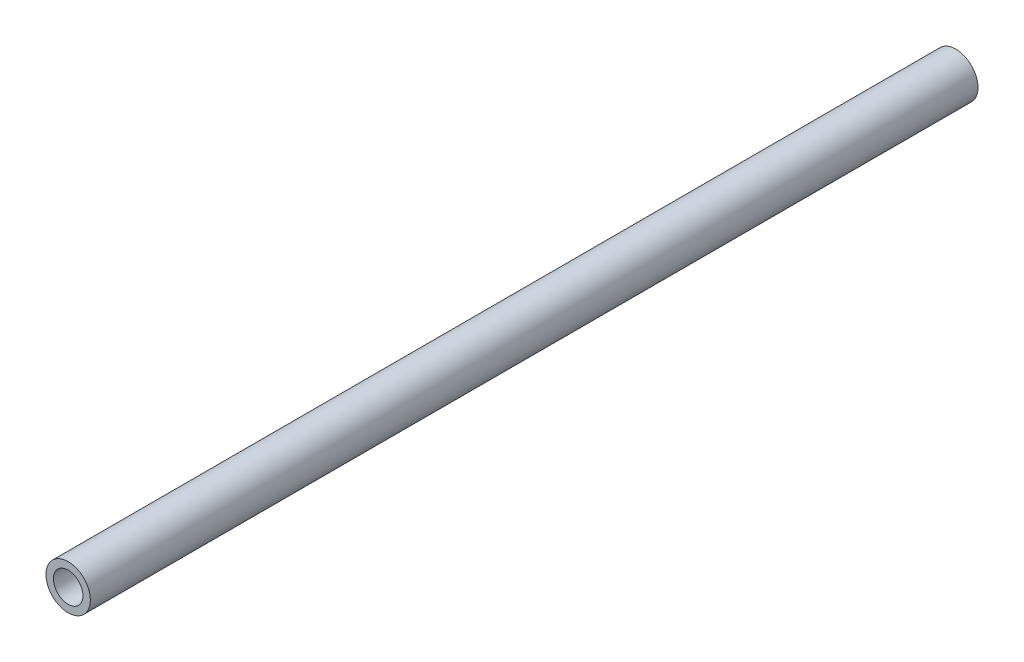
SolidWorks part; units mm, degrees
ref_plane "Front Plane" through (0, 0, 0) normal (0, 0, 1) x (1, 0, 0)
ref_plane "Top Plane" through (0, 0, 0) normal (0, 1, 0) x (1, 0, 0)
ref_plane "Right Plane" through (0, 0, 0) normal (1, 0, 0) x (0, 0, -1)
sketch "Sketch1" plane through (0, 0, 0) normal (0, 0, 1) x (1, 0, 0)
  circle A0 centre (0, 0) radius 6.35
  circle A1 centre (0, 0) radius 9.525
  dimension "D1" = 12.7
  dimension "D2" = 19.05
extrude "Boss-Extrude1" add sketch "Sketch1" along normal blind 381
equation "\"span\"= 48"
equation "\"wing_chord\"= 9"
equation "\"fuse_len\"= 15"
equation "\"fuse_height\"= 5"
equation "\"fuse_wid\"= 5"
equation "\"foam_t\"= 0.1875"
equation "\"main_spar_len\"= 36"
equation "\"x_fuse_to_wing\"= 3"
equation "\"x_cg_from_le\"= 2.25"
equation "\"boom_len\"= 30"
equation "\"D1@Boss-Extrude1\"= \"boom_len\"/2"
